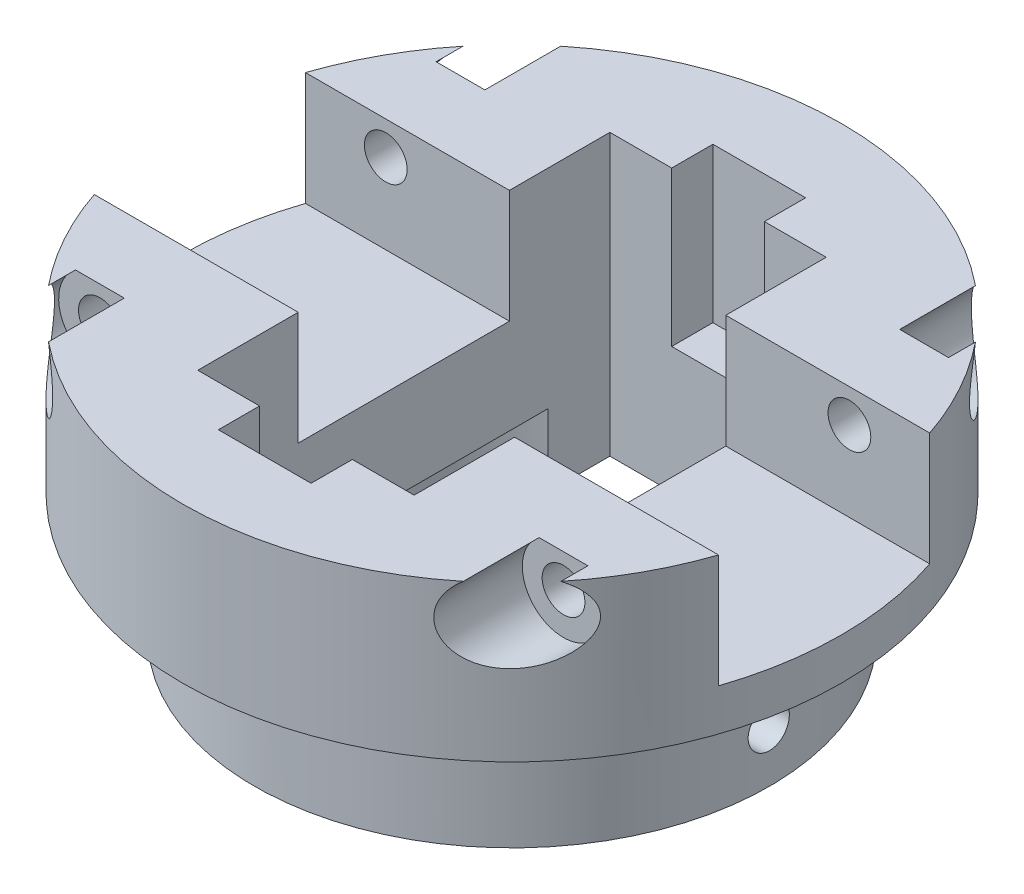
SolidWorks part; units mm, degrees
material "Polylactide (PLA)"
ref_plane "Front Plane" through (0, 0, 0) normal (0, 0, 1) x (1, 0, 0)
ref_plane "Top Plane" through (0, 0, 0) normal (0, 1, 0) x (1, 0, 0)
ref_plane "Right Plane" through (0, 0, 0) normal (1, 0, 0) x (0, 0, -1)
sketch "Sketch1" plane through (0, 0, 0) normal (0, 1, 0) x (1, 0, 0)
  circle A0 centre (0, 0) radius 22
  dimension "D1" = 44
extrude "Boss-Extrude1" add sketch "Sketch1" along normal blind 5
sketch "Sketch2" plane through (0, 5, 0) normal (0, 1, 0) x (1, 0, 0)
  circle A0 centre (0, 0) radius 25
  dimension "D1" = 50
extrude "Boss-Extrude2" add sketch "Sketch2" along normal blind 5
sketch "Sketch3" plane through (0, 10, 0) normal (0, 1, 0) x (1, 0, 0)
  circle A0 centre (0, 0) radius 7.5
  dimension "D1" = 15
extrude "Cut-Extrude1" cut sketch "Sketch3" against normal blind 16
sketch "Sketch4" plane through (0, 0, 0) normal (1, 0, 0) x (0, 0, -1)
  line L0 (-7.5, 0) -> (7.5, 0) construction
  line L1 (-9.6176, 7.2785) -> (-16.698, 7.2785)
  line L2 (-16.698, 7.2785) -> (-31.9838, 12.1645)
  line L3 (-31.9838, 12.1645) -> (-31.9838, 27.2229)
  line L4 (-31.9838, 27.2229) -> (-9.6176, 27.2229)
  line L5 (-9.6176, 27.2229) -> (-9.6176, 7.2785)
  line L6 (0, 0) -> (0, 17.3451) construction
  point P4 (0, 0)
  dimension "D1" = 15
revolve "Revolve1" add sketch "Sketch4" angle 360 about L6
sketch "Sketch5" plane through (0, 27.2229, 0) normal (0, 1, 0) x (1, 0, 0)
  line L1 (-36.0604, 10.25) -> (36.0604, 10.25)
  line L2 (-36.0604, 10.25) -> (-36.0604, -10.25)
  line L3 (-36.0604, -10.25) -> (36.0604, -10.25)
  line L4 (36.0604, 10.25) -> (36.0604, -10.25)
  line L5 (-36.0604, 10.25) -> (36.0604, -10.25) construction
  line L6 (-36.0604, -10.25) -> (36.0604, 10.25) construction
  point P0 (0, 0)
  dimension "D1" = 20.5
  dimension "D2" = 72.1207
extrude "Cut-Extrude2" cut sketch "Sketch5" against normal blind 11
sketch "Sketch6" plane through (0, 0, 0) normal (0, 0, 1) x (1, 0, 0)
  circle A0 centre (-22.5, 24) radius 2.075
  circle A1 centre (22.5, 24) radius 2.075
  dimension "D4" = 4.15
  dimension "D5" = 4.15
  dimension "D1" = 45
  dimension "D2" = 22.5
  dimension "D3" = 24
extrude "Cut-Extrude3" cut sketch "Sketch6" against normal through all both and the other way through all
sketch "Sketch7" plane through (0, 5, 0) normal (0, -1, 0) x (1, 0, 0)
  circle A0 centre (0, 0) radius 25
  circle A1 centre (0, 0) radius 12.5
  dimension "D1" = 50
  dimension "D2" = 25
extrude "Boss-Extrude3" add sketch "Sketch7" along normal blind 5
sketch "Sketch8" plane through (0, 0, 0) normal (1, 0, 0) x (0, 0, -1)
  circle A0 centre (0, 5) radius 2
  dimension "D1" = 4
  dimension "D2" = 5
extrude "Cut-Extrude4" cut sketch "Sketch8" against normal through all both and the other way through all
sketch "Sketch9" plane through (0, 27.2229, 0) normal (0, 1, 0) x (1, 0, 0)
  line L1 (-10.5, 20) -> (10.5, 20)
  line L2 (-10.5, 20) -> (-10.5, -20)
  line L3 (-10.5, -20) -> (10.5, -20)
  line L4 (10.5, 20) -> (10.5, -20)
  line L5 (-10.5, 20) -> (10.5, -20) construction
  line L6 (-10.5, -20) -> (10.5, 20) construction
  point P0 (0, 0)
  dimension "D1" = 21
  dimension "D2" = 40
extrude "Cut-Extrude5" cut sketch "Sketch9" against normal blind 31
sketch "Sketch11" plane through (0, 0, 0) normal (0, -1, 0) x (1, 0, 0)
  circle A0 centre (0, 0) radius 17.5
  dimension "D1" = 35
extrude "Cut-Extrude7" cut sketch "Sketch11" against normal blind 7
sketch "Sketch14" plane through (0, 0, 0) normal (0, 0, 1) x (1, 0, 0)
  circle A0 centre (22.5, 24) radius 4
  dimension "D1" = 8
extrude "Cut-Extrude10" cut sketch "Sketch14" against normal blind 9 from offset 26.5
sketch "Sketch21" plane through (0, 27.2229, 0) normal (0, 1, 0) x (1, 0, 0)
  line L5 (-4.5, -20) -> (4.5, -20)
  line L6 (-4.5, -20) -> (-4.5, -24)
  line L7 (-4.5, -24) -> (4.5, -24)
  line L8 (4.5, -20) -> (4.5, -24)
  dimension "D2" = 9
  dimension "D3" = 4
extrude "Cut-Extrude12" cut sketch "Sketch21" against normal blind 15
sketch "Sketch22" plane through (0, 27.2229, 0) normal (0, 1, 0) x (1, 0, 0)
  line L5 (-4.5, 20) -> (4.5, 20)
  line L6 (-4.5, 20) -> (-4.5, 24)
  line L7 (-4.5, 24) -> (4.5, 24)
  line L8 (4.5, 20) -> (4.5, 24)
  dimension "D2" = 9
  dimension "D3" = 4
extrude "Cut-Extrude13" cut sketch "Sketch22" against normal blind 15
sketch "Sketch24" plane through (0, 0, 0) normal (0, 0, 1) x (1, 0, 0)
  circle A0 centre (22.5, 24) radius 4
extrude "Cut-Extrude14" cut sketch "Sketch24" against normal blind 15 from offset 17.5 offset against normal yes
sketch "Sketch25" plane through (0, 0, 0) normal (0, 0, 1) x (1, 0, 0)
  circle A0 centre (-22.5, 24) radius 4
  dimension "D1" = 8
extrude "Cut-Extrude15" cut sketch "Sketch25" against normal blind 15 from offset 17.5 offset against normal yes
sketch "Sketch26" plane through (0, 0, 0) normal (0, 0, 1) x (1, 0, 0)
  circle A0 centre (-22.5, 24) radius 4
  dimension "D1" = 8
extrude "Cut-Extrude16" cut sketch "Sketch26" along normal blind 15 from offset 17.5
